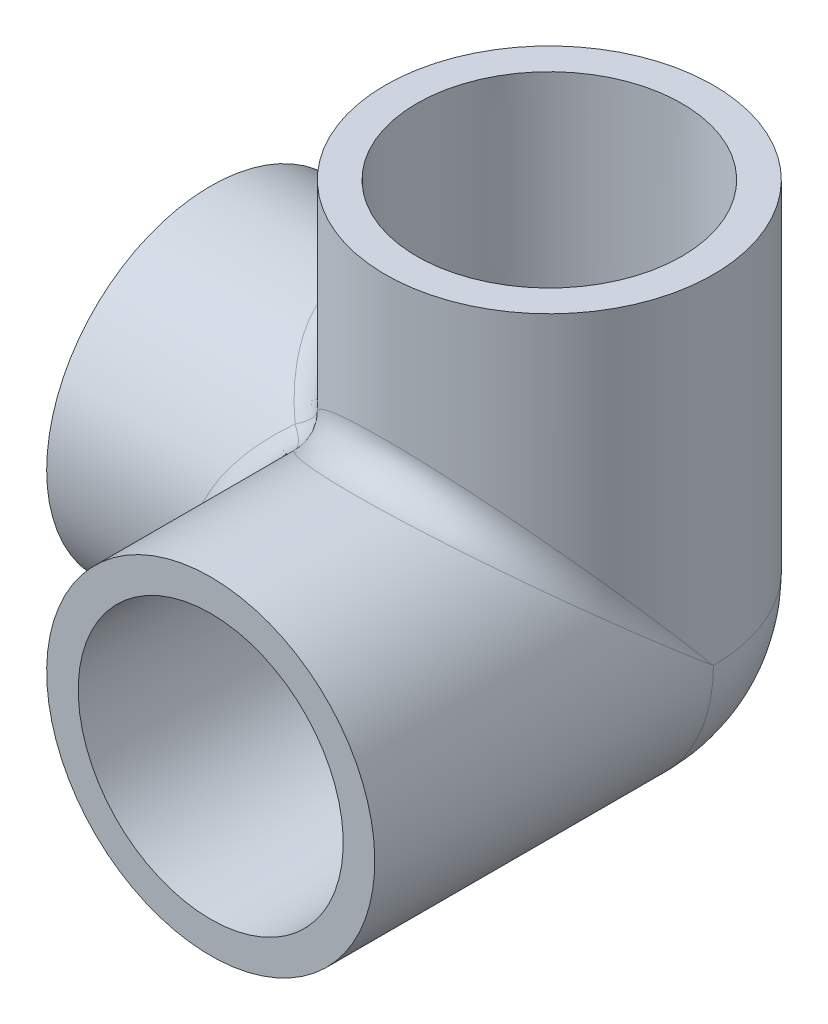
SolidWorks part; units mm, degrees
ref_plane "Front Plane" through (0, 0, 0) normal (0, 0, 1) x (1, 0, 0)
ref_plane "Top Plane" through (0, 0, 0) normal (0, 1, 0) x (1, 0, 0)
ref_plane "Right Plane" through (0, 0, 0) normal (1, 0, 0) x (0, 0, -1)
sketch "Sketch0" plane through (0, 0, 0) normal (0, 0, 1) x (1, 0, 0)
  line L0 (-34.3408, 0) -> (0, 0) construction
  line L1 (0, 0) -> (0, 34.3408) construction
  line L2 (-14.2748, 0) -> (0, 0) construction
  line L3 (0, 0) -> (0, 14.2748) construction
  line L4 (-34.3408, 16.637) -> (-34.3408, -16.637) construction
  line L5 (-14.2748, 13.2842) -> (-34.3408, 13.4366) construction
  line L6 (-14.2748, 13.2842) -> (-14.2748, -13.2842) construction
  line L7 (-14.2748, -13.2842) -> (-34.3408, -13.4366) construction
  line L8 (-34.3408, 13.4366) -> (-34.3408, -13.4366) construction
  line L9 (-16.637, 34.3408) -> (16.637, 34.3408) construction
  line L10 (-13.4366, 34.3408) -> (13.4366, 34.3408) construction
  line L11 (13.4366, 34.3408) -> (13.2842, 14.2748) construction
  line L12 (13.2842, 14.2748) -> (-13.2842, 14.2748) construction
  line L13 (-13.2842, 14.2748) -> (-13.4366, 34.3408) construction
  line L14 (-14.2748, 10.4648) -> (-14.2748, -10.4648) construction
  line L18 (-10.4648, 14.2748) -> (10.4648, 14.2748) construction
  dimension "H" = 34.3408
  dimension "G" = 14.2748
  dimension "M" = 33.274
  dimension "OD A" = 26.8732
  dimension "OD B" = 26.5684
  dimension "ID" = 20.9296
sketch "Sketch1" plane through (0, 0, 0) normal (0, 0, 1) x (1, 0, 0)
  line L0 (-34.3408, 0) -> (16.637, 0)
  line L1 (-34.3408, 0) -> (-34.3408, -16.637)
  line L2 (-34.3408, -16.637) -> (0, -16.637)
  arc A0 (0, -16.637) -> (16.637, 0) centre (0, 0) ccw
  dimension "D1" = 50.9778
revolve "Revolve1" add sketch "Sketch1" angle 360 about L0
sketch "Sketch2" plane through (0, 0, 0) normal (0, 0, 1) x (1, 0, 0)
  line L0 (16.637, 34.3408) -> (0, 34.3408)
  line L4 (0, 34.3408) -> (0, -16.637)
  line L5 (16.637, 0) -> (16.637, 34.3408)
  arc A0 (16.637, 0) -> (0, -16.637) centre (0, 0) cw
revolve "Revolve2" add sketch "Sketch2" angle 360 about L4
sketch "Sketch3" plane through (0, 0, 0) normal (1, 0, 0) x (0, 0, -1)
  line L0 (16.637, 0) -> (-34.3408, 0)
  line L1 (-34.3408, 0) -> (-34.3408, -16.637)
  line L2 (-34.3408, -16.637) -> (0, -16.637)
  arc A0 (0, -16.637) -> (16.637, 0) centre (0, 0) ccw
  dimension "D1" = 50.9778
revolve "Revolve3" add sketch "Sketch3" angle 360 about L0
sketch "Sketch4" plane through (0, 0, 0) normal (0, 0, 1) x (1, 0, 0)
  line L0 (-34.3408, 0) -> (10.4648, 0)
  line L1 (-34.3408, 16.637) -> (-34.3408, -16.637) construction
  line L2 (0, -10.4648) -> (-14.2748, -10.4648)
  line L3 (-14.2748, -10.4648) -> (-14.2748, -13.2842)
  line L4 (-14.2748, -13.2842) -> (-34.3408, -13.4366)
  line L5 (-34.3408, -13.4366) -> (-34.3408, 0)
  arc A0 (10.4648, 0) -> (0, -10.4648) centre (0, 0) cw
  dimension "D1" = 20.066
revolve "Cut-Revolve1" cut sketch "Sketch4" angle 360 about L0
sketch "Sketch5" plane through (0, 0, 0) normal (0, 0, 1) x (1, 0, 0)
  line L0 (0, 34.3408) -> (0, -10.4648)
  line L1 (10.4648, 0) -> (10.4648, 14.2748)
  line L2 (10.4648, 14.2748) -> (13.2842, 14.2748)
  line L3 (13.2842, 14.2748) -> (13.4366, 34.3408)
  line L4 (0, 34.3408) -> (13.4366, 34.3408)
  arc A0 (0, -10.4648) -> (10.4648, 0) centre (0, 0) ccw
revolve "Cut-Revolve2" cut sketch "Sketch5" angle 360 about L0
sketch "Sketch6" plane through (0, 0, 0) normal (1, 0, 0) x (0, 0, -1)
  line L0 (10.4648, 0) -> (-34.3408, 0)
  line L1 (-34.3408, 0) -> (-34.3408, -13.4366)
  line L2 (-34.3408, -13.4366) -> (-14.2748, -13.2842)
  line L3 (-14.2748, -13.2842) -> (-14.2748, -10.4648)
  line L4 (-14.2748, -10.4648) -> (0, -10.4648)
  line L5 (-10.4648, 0) -> (10.4648, 0) construction
  line L6 (-34.3408, 16.637) -> (-34.3408, -16.637) construction
  arc A0 (0, -10.4648) -> (10.4648, 0) centre (0, 0) ccw
  dimension "D1" = 20.066
revolve "Cut-Revolve3" cut sketch "Sketch6" angle 360 about L0
fillet "Fillet1" radius 3.2004 6 edges at (-15.3706, -6.3667, 15.3706) (6.3667, 15.3706, 15.3706) (-15.3706, 15.3706, -6.3667) (-9.6682, -4.0047, 9.6682) (-9.6682, 9.6682, -4.0047) (4.0047, 9.6682, 9.6682)
equation "\"D1@Sketch3\" = \"D1@Sketch1\""
equation "\"D1@Sketch6\" = \"D1@Sketch4\""
equation "\"D1@Fillet1\" =  ( \"M@Sketch0\" - \"OD A@Sketch0\" )  / 2"
